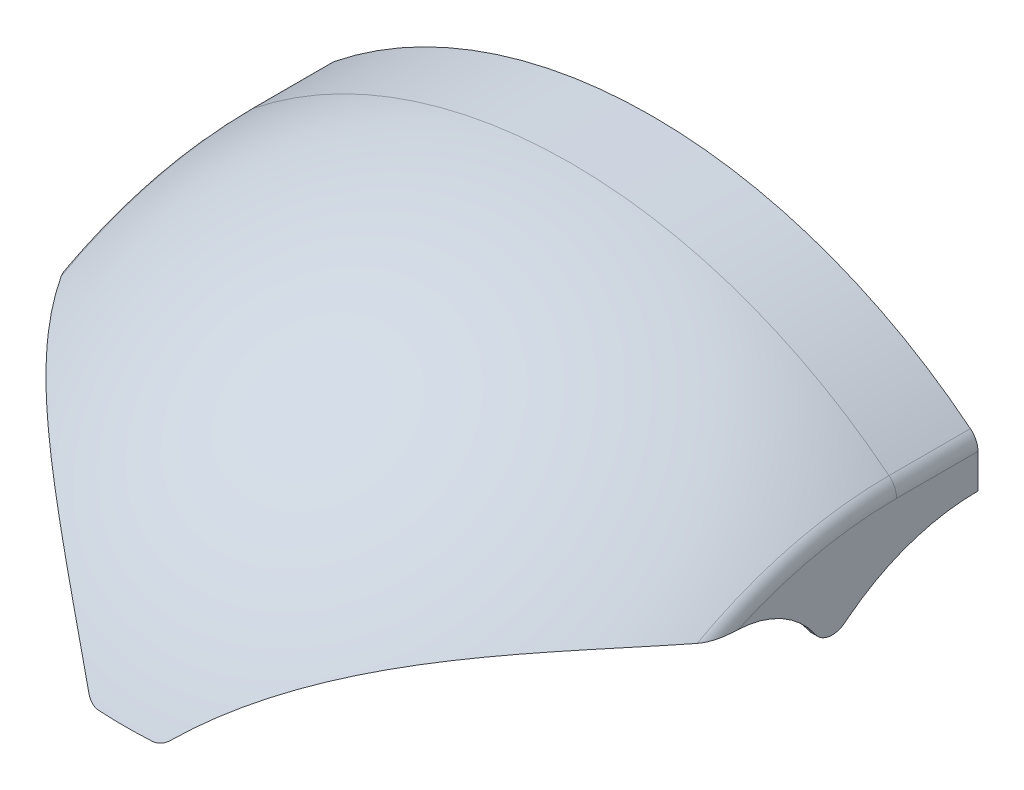
SolidWorks part; units mm, degrees
material "ABS"
ref_plane "Front Plane" through (0, 0, 0) normal (0, 0, 1) x (1, 0, 0)
ref_plane "Top Plane" through (0, 0, 0) normal (0, 1, 0) x (1, 0, 0)
ref_plane "Right Plane" through (0, 0, 0) normal (1, 0, 0) x (0, 0, -1)
sketch "Sketch1" plane through (0, 0, 0) normal (0, 1, 0) x (1, 0, 0)
  line L0 (-65, 40.8579) -> (-47.3223, 58.5355) construction
  line L1 (0, -65.9841) -> (0, 65.9841) construction
  line L2 (0, -58.5355) -> (0, 0) construction
  line L3 (0, 0) -> (-47.3223, 0) construction
  line L4 (65, 40.8579) -> (47.3223, 58.5355) construction
  line L5 (65, -40.8579) -> (47.3223, -58.5355) construction
  line L6 (-65, -40.8579) -> (-47.3223, -58.5355) construction
  line L7 (-47.3223, -58.5355) -> (47.3223, -58.5355) construction
  line L8 (47.3223, -58.5355) -> (47.3223, 58.5355) construction
  line L9 (47.3223, 58.5355) -> (-47.3223, 58.5355) construction
  line L10 (-47.3223, 58.5355) -> (-47.3223, -58.5355) construction
  circle A0 centre (-47.3223, 58.5355) radius 1.45
  circle A1 centre (-65, 40.8579) radius 1.45
  circle A2 centre (65, 40.8579) radius 1.45
  circle A3 centre (47.3223, 58.5355) radius 1.45
  circle A4 centre (65, -40.8579) radius 1.45
  circle A5 centre (47.3223, -58.5355) radius 1.45
  circle A6 centre (-47.3223, -58.5355) radius 1.45
  circle A7 centre (-65, -40.8579) radius 1.45
  dimension "D9" = 2.9
  dimension "D7" = 130
  dimension "D1" = 25
  dimension "D2" = 45
  dimension "D3" = 90
  dimension "D4" = 90
  dimension "D5" = 90
  dimension "D6" = 117.0711
sketch "Sketch2" plane through (0, 0, 0) normal (0, 1, 0) x (1, 0, 0)
  line L0 (158.75, -25.4) -> (-158.75, -25.4)
  line L1 (0, -25.4) -> (0, 0) construction
  arc A0 (158.75, -25.4) -> (-158.75, -25.4) centre (0, -25.4) cw
  dimension "D2" = 25.4
  dimension "D1" = 317.5
revolve "Revolve1" add sketch "Sketch2" angle 90 about L0
shell "Shell1" thickness 1.5875 removed face at (0, 0, 104.775) removed face at (0, 79.375, 25.4)
sketch "Sketch4" plane through (0, 0, 0) normal (0, 1, 0) x (1, 0, 0)
  line L0 (-64.2434, -34.4303) -> (-57.0592, -27.2461)
  line L1 (-64.2434, -34.4303) -> (-40.8947, -57.7789)
  line L2 (-57.0592, -27.2461) -> (-33.7105, -50.5947)
  line L3 (-40.8947, -57.7789) -> (-33.7105, -50.5947)
  line L4 (-64.2434, -34.4303) -> (-33.7105, -50.5947) construction
  line L5 (-57.0592, -27.2461) -> (-40.8947, -57.7789) construction
  line L6 (-65, -40.8579) -> (-47.3223, -58.5355) construction
  line L7 (64.2434, -34.4303) -> (57.0592, -27.2461)
  line L8 (64.2434, -34.4303) -> (40.8947, -57.7789)
  line L9 (57.0592, -27.2461) -> (33.7105, -50.5947)
  line L10 (40.8947, -57.7789) -> (33.7105, -50.5947)
  line L11 (64.2434, -34.4303) -> (33.7105, -50.5947) construction
  line L12 (57.0592, -27.2461) -> (40.8947, -57.7789) construction
  line L13 (65, -40.8579) -> (47.3223, -58.5355) construction
  line L14 (48.977, -42.5125) -> (56.1612, -49.6967) construction
  line L15 (-48.977, -42.5125) -> (-56.1612, -49.6967) construction
  point P1 (-48.977, -42.5125)
  point P4 (48.977, -42.5125)
  point P8 (0, 0)
  dimension "D1" = 33.02
  dimension "D2" = 10.16
  dimension "D3" = 33.02
  dimension "D4" = 10.16
  dimension "D5" = 90
  dimension "D6" = 10.16
  dimension "D7" = 10.16
extrude "Boss-Extrude1" add sketch "Sketch4" along normal up to next
sketch "Sketch8" plane through (0, 0, 0) normal (0, 0, 1) x (1, 0, 0)
  line L0 (158.75, 0) -> (157.1625, 0) construction
  line L1 (158.75, 0) -> (-158.75, 0)
  line L2 (158.75, 0) -> (158.75, 76.2)
  line L3 (158.75, 76.2) -> (-158.75, 76.2)
  line L4 (-158.75, 0) -> (-158.75, 76.2)
  line L5 (158.75, 0) -> (-158.75, 76.2) construction
  line L6 (158.75, 76.2) -> (-158.75, 0) construction
  point P4 (0, 38.1)
  dimension "D1" = 76.2
extrude "Cut-Extrude3" cut sketch "Sketch8" along normal through all
sketch "Sketch14" plane through (0, 0, 0) normal (0, 1, 0) x (1, 0, 0)
  line L1 (48.0789, -64.9631) -> (71.4276, -41.6145)
  line L2 (48.0789, -64.9631) -> (40.8947, -57.7789)
  line L3 (40.8947, -57.7789) -> (64.2434, -34.4303)
  line L4 (71.4276, -41.6145) -> (64.2434, -34.4303)
  line L5 (64.2434, -34.4303) -> (40.8947, -57.7789) construction
  point P4 (70.5753, -41.2826)
  point P5 (36.1199, -61.603)
  point P7 (64.2434, -34.4303)
  point P9 (56.3347, -27.9706)
  point P10 (39.7676, -58.9061)
  point P11 (56.1124, -28.1929)
  point P15 (0, 0)
  point P16 (0, 0)
  dimension "D1" = 10.16
extrude "Boss-Extrude4" add sketch "Sketch14" along normal blind 6.35 from surface starting at face at (48.977, 76.2, 42.5125)
sketch "Sketch15" plane through (0, 82.55, 0) normal (0, 1, 0) x (1, 0, 0)
  circle A0 centre (65, -40.8579) radius 1.45
  circle A1 centre (47.3223, -58.5355) radius 1.45
  circle A2 centre (65, -40.8579) radius 1.45 construction
  circle A3 centre (47.3223, -58.5355) radius 1.45 construction
extrude "Cut-Extrude6" cut sketch "Sketch15" against normal blind 6.35
mirror "Mirror1" about plane through (0, 0, 0) normal (1, 0, 0) of "Cut-Extrude6", "Boss-Extrude4"
sketch "Sketch9" plane through (0, 0, 0) normal (0, 1, 0) x (1, 0, 0)
  line L0 (-101.6, 254) -> (-139.2664, 254)
  line L1 (-101.6, -254) -> (101.6, -254) construction
  line L2 (-101.6, -254) -> (-101.6, 254)
  line L3 (-101.6, 254) -> (101.6, 254) construction
  line L4 (101.6, -254) -> (101.6, 254)
  line L5 (-101.6, -254) -> (101.6, 254) construction
  line L6 (-101.6, 254) -> (101.6, -254) construction
  line L7 (-139.2664, 254) -> (-139.2664, -254)
  line L8 (-139.2664, -254) -> (-101.6, -254)
  line L9 (101.6, -254) -> (139.2664, -254)
  line L10 (139.2664, -254) -> (139.2664, 254)
  line L11 (139.2664, 254) -> (101.6, 254)
  point P4 (0, 0)
  dimension "D1" = 254
  dimension "D2" = 203.2
extrude "Cut-Extrude4" cut sketch "Sketch9" along normal through all
sketch "Sketch11" plane through (0, 0, 25.4) normal (0, 0, -1) x (-1, 0, 0)
  line L1 (-101.6, 76.2) -> (-99.695, 76.2)
  line L2 (-101.6, 76.2) -> (-101.6, 119.9062)
  line L3 (-101.6, 119.9062) -> (-99.695, 123.0484)
  line L4 (-99.695, 76.2) -> (-99.695, 123.0484)
  line L5 (101.6, 76.2) -> (99.695, 76.2)
  line L6 (101.6, 76.2) -> (101.6, 119.9062)
  line L7 (101.6, 119.9062) -> (99.695, 122.5513)
  line L8 (99.695, 76.2) -> (99.695, 122.5513)
  point P4 (0, 0)
  point P5 (0, 0)
  point P6 (99.2896, 121.8262)
  point P7 (99.3672, 122.5513)
  dimension "D1" = 1.905
  dimension "D2" = 1.905
extrude "Boss-Extrude3" add sketch "Sketch11" against normal up to surface (92.58 mm away) up to face at (-49.0367, 147.8179, 42.4724)
sketch "Sketch10" plane through (0, 0, 25.4) normal (0, 0, -1) x (-1, 0, 0)
  line L2 (-99.695, 76.2) -> (-99.695, 121.4947) construction
  line L3 (-101.6, 121.9795) -> (-101.6, 76.2)
  line L4 (-101.6, 76.2) -> (-99.695, 76.2)
  line L5 (-99.695, 76.2) -> (-99.695, 121.4947)
  line L6 (99.695, 121.4947) -> (99.695, 76.2)
  line L7 (99.695, 76.2) -> (101.6, 76.2)
  line L8 (101.6, 76.2) -> (101.6, 121.9795)
  arc A0 (-99.695, 121.4947) -> (99.695, 121.4947) centre (0, 0) cw
  arc A1 (-101.6, 121.9795) -> (101.6, 121.9795) centre (0, 0) cw
  arc A2 (101.6, 121.9795) -> (-101.6, 121.9795) centre (0, 0) ccw construction
  arc A3 (99.695, 121.4947) -> (-99.695, 121.4947) centre (0, 0) ccw construction
extrude "Boss-Extrude2" add sketch "Sketch10" along normal blind 25.4
sketch "Sketch12" plane through (0, 0, 0) normal (0, 0, 1) x (1, 0, 0)
  line L0 (-88.9, 0) -> (88.9, 0) construction
  arc A2 (0, 63.0697) -> (0, -63.0697) centre (-88.9, 0) ccw
  arc A3 (0, 63.0697) -> (0, -63.0697) centre (88.9, 0) cw
  point P3 (0, 0)
  point P4 (108.0511, 0)
  point P8 (0, -22.1151)
  point P10 (0, -41.8295)
  point P11 (-24.1617, -80.7143)
  point P12 (14.2703, -62.5314)
  point P13 (-23.6612, 0)
  point P14 (0, 0)
  point P15 (6.7857, 19.9254)
  point P16 (42.7814, 21.9128)
  point P17 (30.7115, 21.1086)
  point P18 (-23.6612, 0)
  point P19 (0, 0)
  point P20 (0, 0)
  point P21 (0, 25.6301)
  point P22 (0, 22.7443)
  point P23 (-10.4577, -31.0149)
  point P24 (-2.7206, -22.1151)
  dimension "D1" = 109
  dimension "D2" = 177.8
extrude "Cut-Extrude5" cut sketch "Sketch12" along normal through all from offset 76.2
sketch "Sketch17" plane through (0, 0, 0) normal (1, 0, 0) x (0, 0, -1)
  line L0 (-50.4466, 94.4258) -> (-46.99, 89.2076)
  line L1 (-46.99, 89.2076) -> (-40.2866, 94.4258)
  line L2 (0, 121.9795) -> (0, 76.2) construction
  line L3 (-81.6076, 108.2576) -> (-76.2, 108.2576) construction
  line L4 (-76.2, 108.2576) -> (-76.2, 76.2)
  line L5 (-76.2, 76.2) -> (0, 76.2)
  line L6 (0, 76.2) -> (0, 108.2576)
  line L7 (0, 76.2) -> (-76.2, 76.2) construction
  line L8 (-40.2866, 94.4258) -> (-50.4466, 94.4258) construction
  arc A0 (-76.2, 108.2576) -> (-50.4466, 94.4258) centre (-76.2, 77.3665) cw
  arc A2 (-40.2866, 94.4258) -> (0, 108.2576) centre (0, 42.6724) cw
  point P12 (-40.5103, 94.2823)
  dimension "D1" = 19.05
  dimension "D2" = 29.21
  dimension "D3" = 10.16
extrude "Cut-Extrude7" cut sketch "Sketch17" along normal through all from offset 76.2
mirror "Mirror2" about plane through (0, 0, 0) normal (1, 0, 0) of "Cut-Extrude7"
fillet "Fillet1" radius 6.35 20 edges at (100.6475, 89.2076, 46.99) (-100.6475, 89.2076, 46.99) (-10.9605, 76.2, 163.3254) (10.9605, 76.2, 163.3254) (-99.695, 118.1922, 53.5349) (-101.6, 121.9795, 12.7) (99.695, 118.1922, 53.5349) (101.6, 118.4994, 54.3292) (-99.695, 121.4947, 12.7) (-101.6, 118.4994, 54.3292) (-33.7105, 113.8114, 50.5947) (71.4276, 79.375, 41.6145) (-48.0789, 79.375, 64.9631) (-71.4276, 79.375, 41.6145) (-57.0592, 111.3135, 27.2461) (48.0789, 79.375, 64.9631) (33.7105, 113.8114, 50.5947) (57.0592, 111.3135, 27.2461) (99.695, 121.4947, 12.7) (101.6, 121.9795, 12.7)
